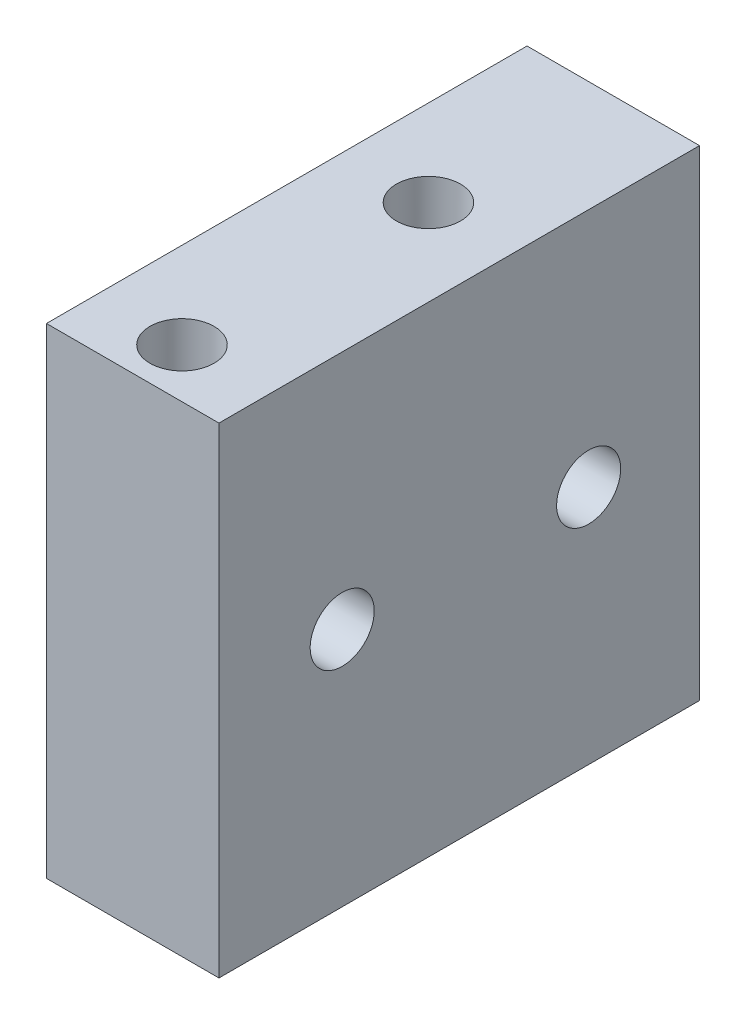
SolidWorks part; units mm, degrees
ref_plane "Front Plane" through (0, 0, 0) normal (0, 0, 1) x (1, 0, 0)
ref_plane "Top Plane" through (0, 0, 0) normal (0, 1, 0) x (1, 0, 0)
ref_plane "Right Plane" through (0, 0, 0) normal (1, 0, 0) x (0, 0, -1)
sketch "Esquisse1" plane through (0, 0, 0) normal (0, 0, 1) x (1, 0, 0)
  line L1 (-3.5, 9.75) -> (3.5, 9.75)
  line L2 (-3.5, 9.75) -> (-3.5, -9.75)
  line L3 (-3.5, -9.75) -> (3.5, -9.75)
  line L4 (3.5, 9.75) -> (3.5, -9.75)
  point P4 (3.5, 0)
  point P5 (0, -9.75)
  point P6 (0, 0)
  dimension "D1" = 7
  dimension "D2" = 19.5
extrude "Main" add sketch "Esquisse1" along normal mid plane 19.5
sketch "Esquisse2" plane through (0, 0, -9.75) normal (0, 0, -1) x (-1, 0, 0)
  line L0 (-3.5, 9.75) -> (3.5, 9.75) construction
  line L1 (3.5, -9.75) -> (-3.5, -9.75) construction
  line L2 (-3.5, -9.75) -> (-3.5, 9.75) construction
  circle A0 centre (1.5, 4.75) radius 1.3
  circle A1 centre (1.5, -4.75) radius 1.3
  dimension "D3" = 2.6
  dimension "D1" = 5
  dimension "D2" = 5
  dimension "D4" = 5
  dimension "D5" = 9.5
extrude "ServoFixingHoles" cut sketch "Esquisse2" against normal blind 10
sketch "Esquisse3" plane through (-3.5, 0, 0) normal (-1, 0, 0) x (0, 0, 1)
  line L0 (9.75, 9.75) -> (9.75, -9.75) construction
  circle A0 centre (4.75, 0) radius 1.3
  circle A1 centre (-5.25, 0) radius 1.3
  point P4 (0, 0)
  point P11 (0, 0)
  dimension "D1" = 2.6
  dimension "D2" = 5
  dimension "D3" = 10
extrude "SideHoles" cut sketch "Esquisse3" against normal through all
sketch "Esquisse4" plane through (0, -9.75, 0) normal (0, -1, 0) x (1, 0, 0)
  line L0 (-3.5, 9.75) -> (3.5, 9.75) construction
  circle A0 centre (0, 7.75) radius 1.3
  circle A1 centre (0, -2.25) radius 1.3
  point P6 (0, 0)
  point P7 (0, 0)
  dimension "D1" = 2.6
  dimension "D2" = 2
  dimension "D3" = 10
extrude "TopHoles" cut sketch "Esquisse4" against normal through all
